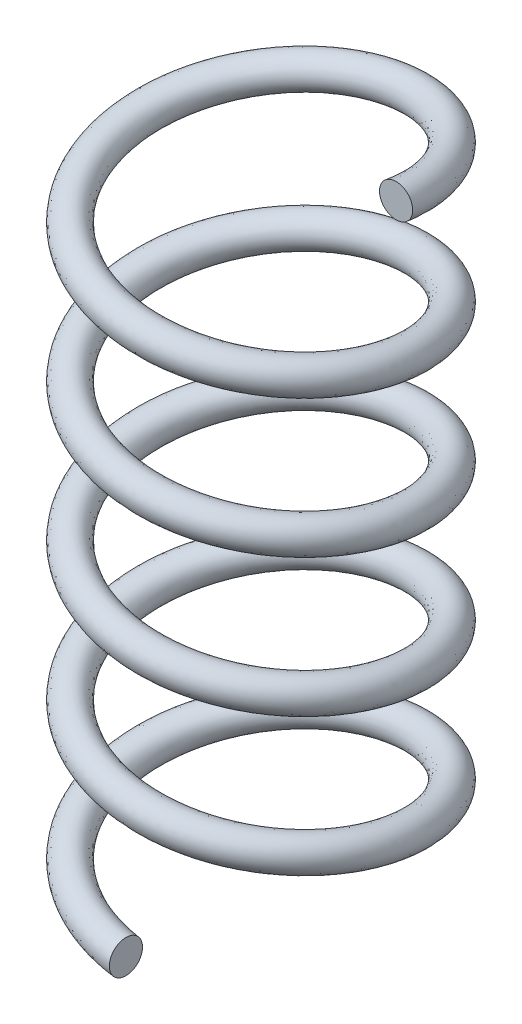
SolidWorks part; units mm, degrees
note: '?' marks a value the reader was unsure of.
ref_plane "Front Plane" through (0, 0, 0) normal (0, 0, 1) x (1, 0, 0)
ref_plane "Top Plane" through (0, 0, 0) normal (0, 1, 0) x (1, 0, 0)
ref_plane "Right Plane" through (0, 0, 0) normal (1, 0, 0) x (0, 0, -1)
sketch "Sketch1" plane through (0, 0, 0) normal (0, 1, 0) x (1, 0, 0)
  circle A0 centre (0, 0) radius 24.5
  dimension "D1" = 49
curve "Helix/Spiral1" pitch 25 height 118.75 turns 4.75
sketch "Sketch7" plane through (0, 0, 0) normal (1, 0, 0) x (0, 0, -1)
  circle A0 centre (-24.5, 0) radius 3.01
  spline S0 degree 3 poles (-24.5, 0) (-24.5, 0.3793) (-23.8228, 1.1424) (-20.8586, 2.2835) (-16.1884, 3.4255) (-10.1941, 4.5673) (-3.366, 5.7091) (3.7373, 6.851) (10.535, 7.9928) (16.471, 9.1346) (21.0599, 10.2764) (23.9263, 11.4183) (24.8358, 12.5601) (23.7139, 13.7019) (20.6525, 14.8438) (15.902, 15.9856) (9.8508, 17.1274) (2.994, 18.2692) (-4.1078, 19.4111) (-10.8735, 20.5529) (-16.75, 21.6947) (-21.2564, 22.8365) (-24.0243, 23.9784) (-24.8273, 25.1202) (-23.5996, 26.262) (-20.4418, 27.4038) (-15.612, 28.5457) (-9.5053, 29.6875) (-2.6212, 30.8293) (4.4773, 31.9712) (11.2096, 33.113) (17.0251, 34.2548) (21.4481, 35.3966) (24.1168, 36.5385) (24.8131, 37.6803) (23.4799, 38.8221) (20.2263, 39.9639) (15.3184, 41.1058) (9.1576, 42.2476) (2.2479, 43.3894) (-4.8458, 44.5313) (-11.5431, 45.6731) (-17.2963, 46.8149) (-21.6348, 47.9567) (-24.2039, 49.0986) (-24.7933, 50.2404) (-23.3549, 51.3822) (-20.0063, 52.524) (-15.0214, 53.6659) (-8.8079, 54.8077) (-1.874, 55.9495) (5.2132, 57.0913) (11.8739, 58.2332) (17.5635, 59.375) (21.8166, 60.5168) (24.2854, 61.6587) (24.7678, 62.8005) (23.2245, 63.9423) (19.7817, 65.0841) (14.7209, 66.226) (8.4561, 67.3678) (1.4997, 68.5096) (-5.5793, 69.6514) (-12.2021, 70.7933) (-17.8268, 71.9351) (-21.9935, 73.0769) (-24.3613, 74.2188) (-24.7367, 75.3606) (-23.0888, 76.5024) (-19.5525, 77.6442) (-14.4171, 78.7861) (-8.1024, 79.9279) (-1.1251, 81.0697) (5.9443, 82.2115) (12.5274, 83.3534) (18.086, 84.4952) (22.1653, 85.637) (24.4317, 86.7788) (24.6999, 87.9207) (22.9479, 89.0625) (19.3189, 90.2043) (14.1099, 91.3462) (7.7469, 92.488) (0.7502, 93.6298) (-6.3078, 94.7716) (-12.8499, 95.9135) (-18.3411, 97.0553) (-22.3321, 98.1971) (-24.4966, 99.3389) (-24.6575, 100.4808) (-22.8017, 101.6226) (-19.0809, 102.7644) (-13.7996, 103.9062) (-7.3896, 105.0481) (-0.3751, 106.1899) (6.67, 107.3317) (13.1695, 108.4736) (18.592, 109.6154) (22.4938, 110.7572) (24.5558, 111.899) (24.6095, 113.0409) (22.6502, 114.1827) (18.8389, 115.3245) (13.4851, 116.4665) (7.0341, 117.6076) (2.3358, 118.3707) (0, 118.75) knots 0 0 0 0 0.009615 0.019231 0.028846 0.038462 0.048077 0.057692 0.067308 0.076923 0.086538 0.096154 0.105769 0.115385 0.125 0.134615 0.144231 0.153846 0.163462 0.173077 0.182692 0.192308 0.201923 0.211538 0.221154 0.230769 0.240385 0.25 0.259615 0.269231 0.278846 0.288462 0.298077 0.307692 0.317308 0.326923 0.336538 0.346154 0.355769 0.365385 0.375 0.384615 0.394231 0.403846 0.413462 0.423077 0.432692 0.442308 0.451923 0.461538 0.471154 0.480769 0.490385 0.5 0.509615 0.519231 0.528846 0.538462 0.548077 0.557692 0.567308 0.576923 0.586538 0.596154 0.605769 0.615385 0.625 0.634615 0.644231 0.653846 0.663462 0.673077 0.682692 0.692308 0.701923 0.711538 0.721154 0.730769 0.740385 0.75 0.759615 0.769231 0.778846 0.788462 0.798077 0.807692 0.817308 0.826923 0.836538 0.846154 0.855769 0.865385 0.875 0.884615 0.894231 0.903846 0.913462 0.923077 0.932692 0.942308 0.951923 0.961538 0.971154 0.980769 0.990385 1 1 1 1 construction
  dimension "D2" = 6.02
  dimension "D1" = 24.5
sweep "Sweep1" add profiles "Sketch7" path "Helix/Spiral1"
ref_axis "Axis1" through (0, 131.3095, 0) along (0, -1, 0)?
